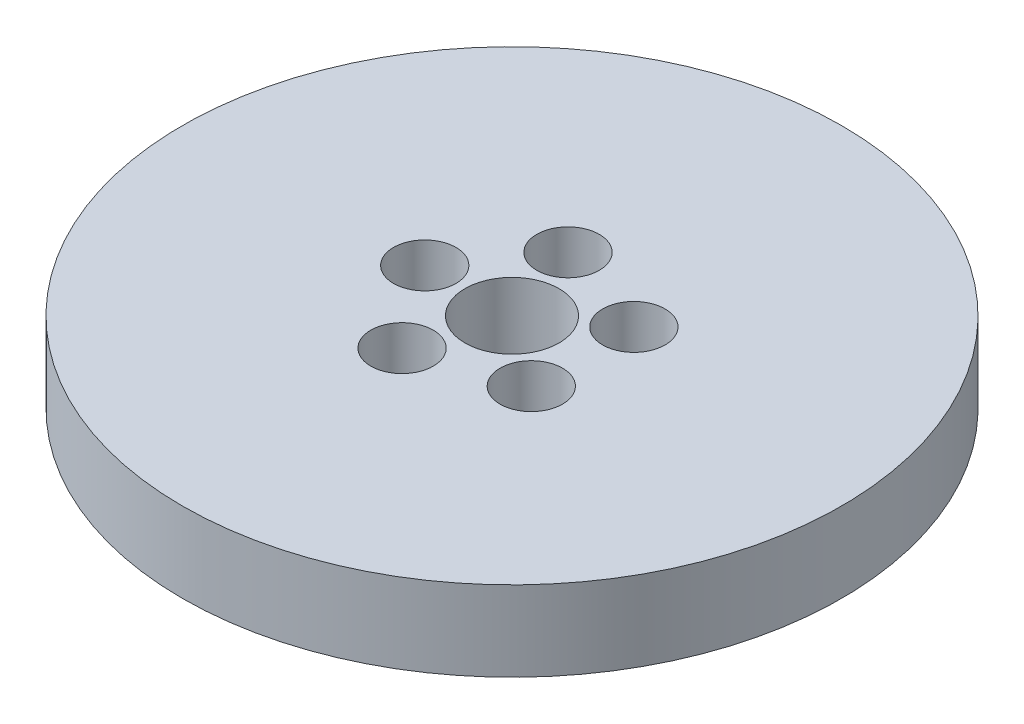
SolidWorks part; units mm, degrees
ref_plane "Front Plane" through (0, 0, 0) normal (0, 0, 1) x (1, 0, 0)
ref_plane "Top Plane" through (0, 0, 0) normal (0, 1, 0) x (1, 0, 0)
ref_plane "Right Plane" through (0, 0, 0) normal (1, 0, 0) x (0, 0, -1)
sketch "Sketch1" plane through (0, 0, 0) normal (0, 1, 0) x (1, 0, 0)
  circle A0 centre (0, 0) radius 70
  dimension "FLANGE_OD" = 140
extrude "Boss-Extrude1" add sketch "Sketch1" along normal blind 17
sketch "Sketch2" plane through (0, 0, 0) normal (0, 1, 0) x (1, 0, 0)
  circle A0 centre (0, 0) radius 10
  dimension "BORE_D" = 20
extrude "Cut-Extrude1" cut sketch "Sketch2" along normal through all
sketch "Sketch3" plane through (0, 17, 0) normal (0, 1, 0) x (1, 0, 0)
  circle A0 centre (0, 0) radius 18.5313 construction
  circle A1 centre (-18.5313, 0) radius 6.6329
  dimension "BOLT_D" = 13.2658
  dimension "BOLT_PCD" = 37.0625
extrude "Cut-Extrude2" cut sketch "Sketch3" against normal blind 14.3658
pattern_circular "CirPattern1" count 5 over 360 about axis through (0, 0, 0) along (0, 1, 0) of "Cut-Extrude2"
